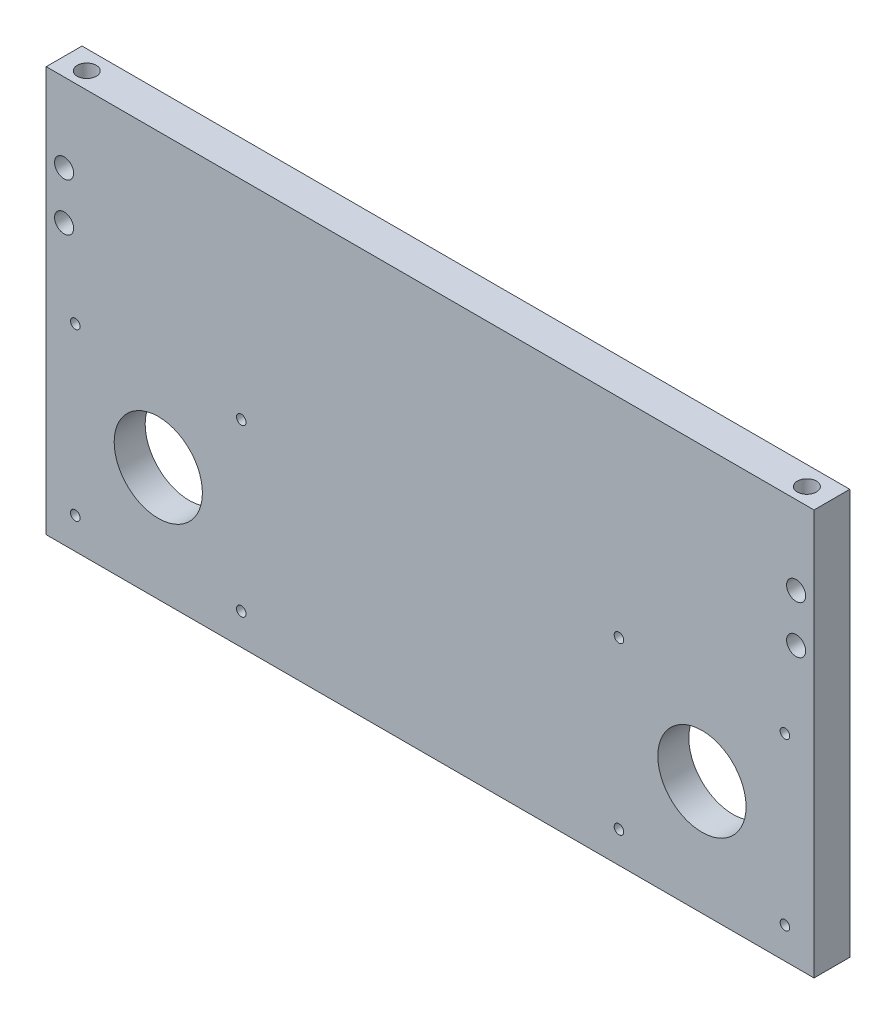
SolidWorks part; units mm, degrees
ref_plane "Płaszczyzna przednia" through (0, 0, 0) normal (0, 0, 1) x (1, 0, 0)
ref_plane "Płaszczyzna górna" through (0, 0, 0) normal (0, 1, 0) x (1, 0, 0)
ref_plane "Płaszczyzna prawa" through (0, 0, 0) normal (1, 0, 0) x (0, 0, -1)
sketch "Szkic1" plane through (0, 0, 0) normal (0, 0, 1) x (1, 0, 0)
  line L1 (161, -85) -> (-161, -85)
  line L2 (161, -85) -> (161, 85)
  line L3 (161, 85) -> (-161, 85)
  line L4 (-161, -85) -> (-161, 85)
  line L5 (161, -85) -> (-161, 85) construction
  line L6 (161, 85) -> (-161, -85) construction
  point P0 (0, 0)
  dimension "D1" = 322
  dimension "D2" = 170
extrude "Dodanie-wyciągnięcie1" add sketch "Szkic1" along normal blind 15
sketch "Szkic2" plane through (0, 0, 15) normal (0, 0, 1) x (1, 0, 0)
  line L2 (-161, -85) -> (161, -85) construction
  line L7 (-161, 85) -> (-161, -85) construction
  circle A1 centre (-148.8, -71.87) radius 2
  dimension "D1" = 13.13
  dimension "D2" = 12.2
  dimension "D5" = 4
extrude "Wytnij-wyciągnięcie2" cut sketch "Szkic2" against normal blind 17.75 contours A1 region at (-148.8, -71.87, 15)
pattern_linear "Szyk liniowy1" count 2 spacing 69.6 along (1, 0, 0) count 2 spacing 69.6 along (0, 1, 0) of "Wytnij-wyciągnięcie2"
sketch "Szkic5" plane through (0, 0, 0) normal (0, 0, -1) x (-1, 0, 0)
  line L1 (161, -85) -> (-161, -85) construction
  line L2 (161, 85) -> (161, -85) construction
  circle A1 centre (114, -37.07) radius 37.5
  dimension "D1" = 47.93
  dimension "D5" = 75
  dimension "D2" = 47
extrude "Wytnij-wyciągnięcie3" cut sketch "Szkic5" against normal blind 2 contours A1 region at (-114, -37.07, 0)
sketch "Szkic7" plane through (0, 0, 2) normal (0, 0, -1) x (-1, 0, 0)
  circle A3 centre (114, -37.07) radius 18.5
  dimension "D1" = 37
extrude "Wytnij-wyciągnięcie4" cut sketch "Szkic7" against normal blind 17.75 contours A3 region at (-114, -37.07, 2)
pattern_linear "Szyk liniowy2" count 2 spacing 228 along (1, 0, 0) of "Wytnij-wyciągnięcie2", "Szyk liniowy1", "Wytnij-wyciągnięcie3", "Wytnij-wyciągnięcie4"
sketch "Szkic8" plane through (0, 85, 0) normal (0, 1, 0) x (1, 0, 0)
  line L0 (-161, -15) -> (-161, 0) construction
  line L1 (161, -15) -> (-161, -15) construction
  line L2 (161, -15) -> (161, 0) construction
  line L3 (161, -15) -> (-161, -15) construction
  circle A0 centre (-151, -8) radius 4
  circle A1 centre (151, -8) radius 4
  dimension "D1" = 10
  dimension "D3" = 8
  dimension "D6" = 8
  dimension "D2" = 7
  dimension "D4" = 10
  dimension "D5" = 7
extrude "Wytnij-wyciągnięcie5" cut sketch "Szkic8" against normal blind 20
sketch "Szkic10" plane through (0, 0, 15) normal (0, 0, 1) x (1, 0, 0)
  line L0 (161, 85) -> (-161, 85) construction
  line L1 (-161, 85) -> (-161, -85) construction
  circle A0 centre (-153.5, 52) radius 4
  circle A1 centre (-153.5, 32) radius 4
  dimension "D1" = 53
  dimension "D3" = 8
  dimension "D4" = 8
  dimension "D2" = 20
  dimension "D5" = 7.5
extrude "Wytnij-wyciągnięcie7" cut sketch "Szkic10" against normal through all
sketch "Szkic11" plane through (0, 0, 15) normal (0, 0, 1) x (1, 0, 0)
  line L0 (161, 85) -> (-161, 85) construction
  line L1 (161, -85) -> (161, 85) construction
  circle A0 centre (153.5, 32) radius 4
  circle A1 centre (153.5, 52) radius 4
  dimension "D1" = 53
  dimension "D2" = 8
  dimension "D3" = 8
  dimension "D4" = 7.5
  dimension "D5" = 20
extrude "Wytnij-wyciągnięcie8" cut sketch "Szkic11" against normal through all
